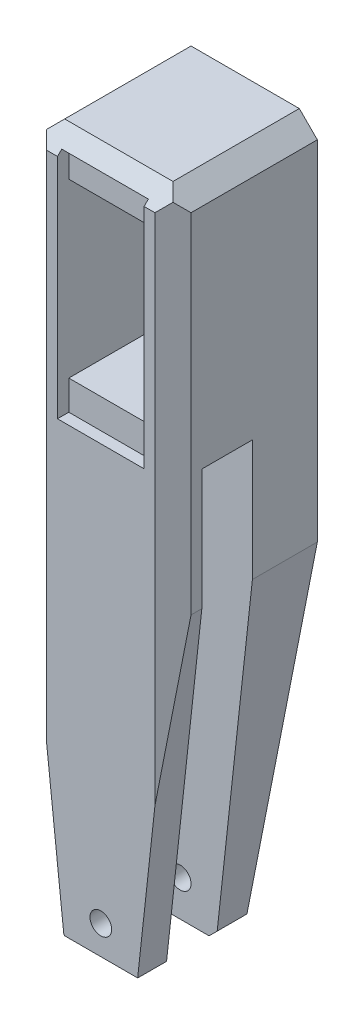
SolidWorks part; units mm, degrees
material "Nylon 101"
ref_plane "Front Plane" through (0, 0, 0) normal (0, 0, 1) x (1, 0, 0)
ref_plane "Top Plane" through (0, 0, 0) normal (0, 1, 0) x (1, 0, 0)
ref_plane "Right Plane" through (0, 0, 0) normal (1, 0, 0) x (0, 0, -1)
sketch "Sketch1" plane through (0, 0, 0) normal (0, 0, 1) x (1, 0, 0)
  line L0 (0, 0) -> (0, -81.5) construction
  line L1 (-10, -10) -> (10, -10)
  line L2 (-10, -10) -> (-10, 10)
  line L3 (-10, 10) -> (10, 10)
  line L4 (10, -10) -> (10, 10)
  line L5 (-10, -10) -> (10, 10) construction
  line L6 (-10, 10) -> (10, -10) construction
  line L7 (-10, -10) -> (-10, -91.5)
  line L8 (-10, -91.5) -> (10, -91.5)
  line L9 (10, -91.5) -> (10, -10)
  circle A0 centre (0, -81.5) radius 1.5
  point P0 (0, 0)
  dimension "D4" = 3
  dimension "D1" = 20
  dimension "D2" = 20
  dimension "D3" = 81.5
  dimension "D5" = 10
extrude "Boss-Extrude1" add sketch "Sketch1" along normal blind 20 contours L8 L9 L1 L7 A0 | L1 L4 L3 L2
chamfer "Chamfer1" distance 2.5 angle 45 12 edges at (0, 10, 0) (0, 10, 20) (10, -91.5, 10) (-10, -91.5, 10) (0, -91.5, 0) (0, -91.5, 20) (-10, -40.75, 0) (-10, -40.75, 20) (10, -40.75, 0) (10, -40.75, 20) (10, 10, 10) (-10, 10, 10)
sketch "Sketch2" plane through (0, -91.5, 0) normal (0, -1, 0) x (1, 0, 0)
  line L0 (0, 0) -> (0, 20) construction
  line L1 (-7.5, 20) -> (7.5, 20) construction
  line L2 (10, 17.5) -> (10, 0) construction
  line L3 (-10, 9) -> (10, 9)
  line L4 (-10, 9) -> (-10, 16)
  line L5 (-10, 16) -> (10, 16)
  line L6 (10, 9) -> (10, 16)
  line L7 (-10, 9) -> (10, 16) construction
  line L8 (-10, 16) -> (10, 9) construction
  point P6 (0, 12.5)
  dimension "D1" = 7
  dimension "D2" = 4
extrude "Cut-Extrude1" cut sketch "Sketch2" against normal blind 65
chamfer "Chamfer2" distance 2.5 angle 45 2 edges at (-10, -26.5, 12.5) (10, -26.5, 12.5)
sketch "Sketch3" plane through (0, 0, 20) normal (0, 0, 1) x (1, 0, 0)
  line L0 (0, -81.5) -> (0, -14) construction
  line L1 (0, -14) -> (0, 3.96)
  line L2 (0, -14) -> (0, -19.84)
  line L3 (0, 3.96) -> (0, 8.09)
  line L4 (0, -19.84) -> (0, -23.97)
  line L5 (0, -23.97) -> (6, -23.97)
  line L6 (6, -23.97) -> (6, 8.09)
  line L7 (6, 8.09) -> (0, 8.09)
  line L8 (-6, 8.09) -> (-6, -23.97)
  line L9 (-6, -23.97) -> (0, -23.97)
  line L10 (-6, 8.09) -> (0, 8.09)
  dimension "D1" = 67.5
  dimension "D2" = 17.96
  dimension "D3" = 5.84
  dimension "D4" = 4.13
  dimension "D5" = 4.13
  dimension "D6" = 32.06
  dimension "D7" = 6
  dimension "D8" = 6
extrude "Cut-Extrude2" cut sketch "Sketch3" against normal blind 1.57
chamfer "Chamfer3" distance 2.5 angle 45 1 edges at (0, 10, 20)
sketch "Sketch4" plane through (0, 0, 18.43) normal (0, 0, 1) x (1, 0, 0)
  line L0 (-6, 8.09) -> (-6, -23.97) construction
  line L1 (-6, 3.99) -> (6, 3.99)
  line L2 (-6, 3.99) -> (-6, -19.87)
  line L3 (-6, -19.87) -> (6, -19.87)
  line L4 (6, 3.99) -> (6, -19.87)
  line L5 (6, -23.97) -> (6, 8.09) construction
  line L6 (6, 8.09) -> (-6, 8.09) construction
  line L7 (-6, -23.97) -> (6, -23.97) construction
  dimension "D1" = 4.1
  dimension "D2" = 4.1
  dimension "D3" = 23.86
extrude "Cut-Extrude3" cut sketch "Sketch4" against normal blind 15.13
sketch "Sketch5" plane through (0, 0, 3.3) normal (0, 0, 1) x (1, 0, 0)
  line L0 (0, 0) -> (0, -19.87) construction
  line L1 (-6, -19.87) -> (6, -19.87) construction
  line L2 (0, -19.87) -> (4.5, -19.87)
  line L3 (4.5, -19.87) -> (4.5, -16.37)
  line L4 (4.5, -16.37) -> (0, -16.37)
  line L5 (0, -16.37) -> (-4.5, -16.37)
  line L6 (-4.5, -16.37) -> (-4.5, -19.87)
  line L7 (-4.5, -19.87) -> (0, -19.87)
  dimension "D1" = 4.5
  dimension "D2" = 3.5
  dimension "D3" = 4.5
extrude "Cut-Extrude4" cut sketch "Sketch5" against normal through all
sketch "Sketch6" plane through (0, 0, 0) normal (0, 0, -1) x (-1, 0, 0)
  circle A0 centre (0, 0) radius 2.77
  dimension "D1" = 5.54
extrude "Cut-Extrude5" cut sketch "Sketch6" against normal through all
sketch "Sketch7" plane through (0, 0, 20) normal (0, 0, 1) x (1, 0, 0)
  line L0 (0, -81.5) -> (0, -91.5) construction
  line L1 (7.5, -91.5) -> (-7.5, -91.5) construction
  line L2 (0, -81.5) -> (0, 0) construction
  line L3 (-10, -40.75) -> (-5, -86.5)
  line L4 (-10, -89) -> (-10, 7.5) construction
  line L5 (5, -86.5) -> (10, -40.75)
  line L6 (10, 7.5) -> (10, -89) construction
  line L9 (10, -40.75) -> (0, -40.75)
  line L10 (0, -40.75) -> (-10, -40.75)
  line L13 (-5, -86.5) -> (5, -86.5)
  line L15 (-10, -40.75) -> (10, -40.75)
  line L16 (-10, -40.75) -> (-10, -91.5)
  line L17 (-10, -91.5) -> (10, -91.5)
  line L18 (10, -40.75) -> (10, -91.5)
  point P21 (0, -86.5)
  line M11 (7.5, -89) -> (7.5, 7.5)
  line M17 (-7.5, 7.5) -> (-7.5, -89)
  line M18 (-7.5, -89) -> (7.5, -89)
  dimension "D1" = 10
extrude "Cut-Extrude6" cut sketch "Sketch7" against normal through all contours L13 L3 L5 M17 M18 M11 | L18 L5 L3 L16 L17 M11 M18 M17
chamfer "Chamfer8" distance 1 angle 45 3 edges at (5, -86.5, 18) (0, -86.5, 20) (-5, -86.5, 18)
sketch "Sketch8" plane through (-10, 0, 0) normal (-1, 0, 0) x (0, 0, 1)
  line L0 (0, -40.75) -> (5, -86.5)
  line L2 (0, -86.5) -> (9, -86.5) construction
  line L3 (0, -40.75) -> (0, -86.5)
  line L4 (0, -86.5) -> (5, -86.5)
  dimension "D1" = 4
extrude "Cut-Extrude7" cut sketch "Sketch8" against normal through all
chamfer "Chamfer9" distance 1 angle 45 3 edges at (5, -86.5, 7) (0, -86.5, 5) (-5, -86.5, 7)
